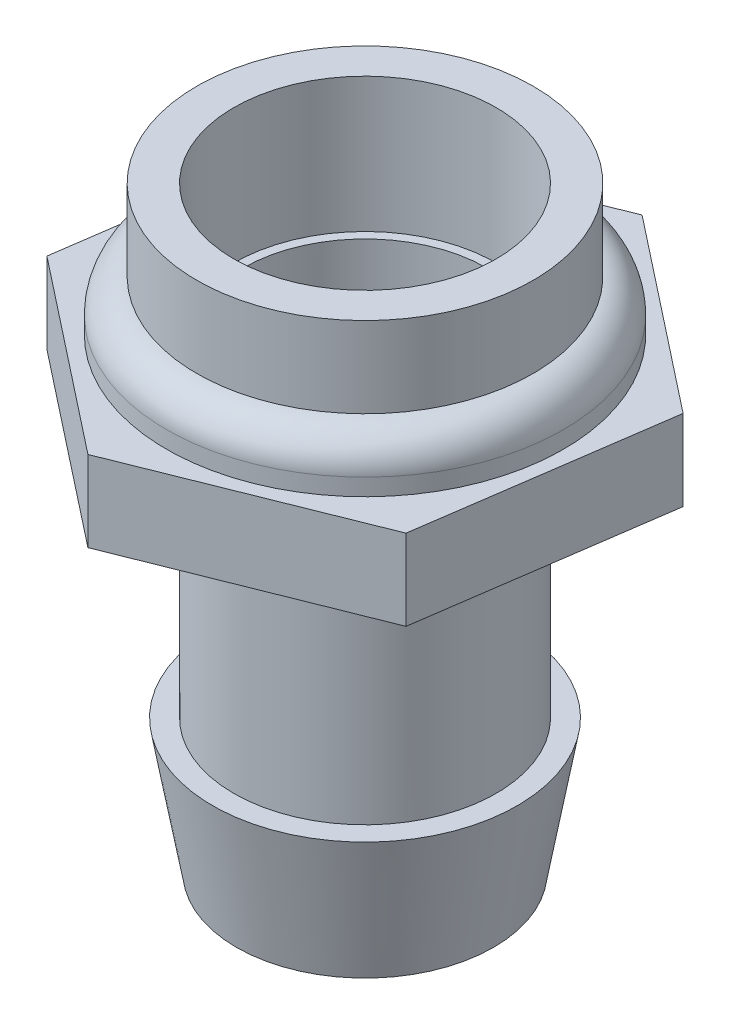
SolidWorks part; units mm, degrees
ref_plane "Front Plane" through (0, 0, 0) normal (0, 0, 1) x (1, 0, 0)
ref_plane "Top Plane" through (0, 0, 0) normal (0, 1, 0) x (1, 0, 0)
ref_plane "Right Plane" through (0, 0, 0) normal (1, 0, 0) x (0, 0, -1)
sketch "Sketch1" plane through (0, 0, 0) normal (0, 1, 0) x (1, 0, 0)
  line L1 (-30.7539, 4.0246) -> (-29.4376, 13.1691)
  line L2 (-29.4376, 13.1691) -> (-36.6988, 18.8813)
  line L3 (-36.6988, 18.8813) -> (-45.2763, 15.4489)
  line L4 (-45.2763, 15.4489) -> (-46.5926, 6.3044)
  line L5 (-46.5926, 6.3044) -> (-39.3314, 0.5922)
  line L6 (-39.3314, 0.5922) -> (-30.7539, 4.0246)
  circle A0 centre (-38.0151, 9.7367) radius 8.001 construction
  dimension "D1" = 16.002
extrude "Boss-Extrude1" add sketch "Sketch1" along normal blind 3.048
sketch "Sketch2" plane through (0, 3.048, 0) normal (0, 1, 0) x (1, 0, 0)
  line L0 (-45.2763, 15.4489) -> (-30.7539, 4.0246) construction
  circle A0 centre (-38.0151, 9.7367) radius 7.493
  dimension "D1" = 14.986
extrude "Boss-Extrude2" add sketch "Sketch2" along normal blind 1.905
sketch "Sketch3" plane through (0, 4.953, 0) normal (0, 1, 0) x (1, 0, 0)
  circle A0 centre (-38.0151, 9.7367) radius 6.35
  dimension "D1" = 12.7
extrude "Boss-Extrude3" add sketch "Sketch3" along normal blind 3.048
sketch "Sketch5" plane through (0, 0, 0) normal (0, -1, 0) x (1, 0, 0)
  line L0 (-29.4376, -13.1691) -> (-46.5926, -6.3044) construction
  circle A0 centre (-38.0151, -9.7367) radius 4.953
  dimension "D1" = 9.906
extrude "Boss-Extrude4" add sketch "Sketch5" along normal blind 9.4742
sketch "Sketch6" plane through (0, -9.4742, 0) normal (0, -1, 0) x (1, 0, 0)
  circle A0 centre (-38.0151, -9.7367) radius 5.7531
  dimension "D1" = 11.5062
extrude "Boss-Extrude5" add sketch "Sketch6" along normal blind 5.08 draft 10
fillet "Fillet3" radius 1.27 1 edges at (-38.0151, 4.953, -2.2437)
sketch "Sketch9" plane through (0, -14.5542, 0) normal (0, -1, 0) x (1, 0, 0)
  circle A0 centre (-38.0151, -9.7367) radius 4.6101
  dimension "D1" = 9.2202
extrude "Cut-Extrude2" cut sketch "Sketch9" against normal through all
sketch "Sketch10" plane through (0, 8.001, 0) normal (0, 1, 0) x (1, 0, 0)
  circle A0 centre (-38.0151, 9.7367) radius 4.953
  dimension "D1" = 9.906
extrude "Cut-Extrude3" cut sketch "Sketch10" against normal blind 5.08
